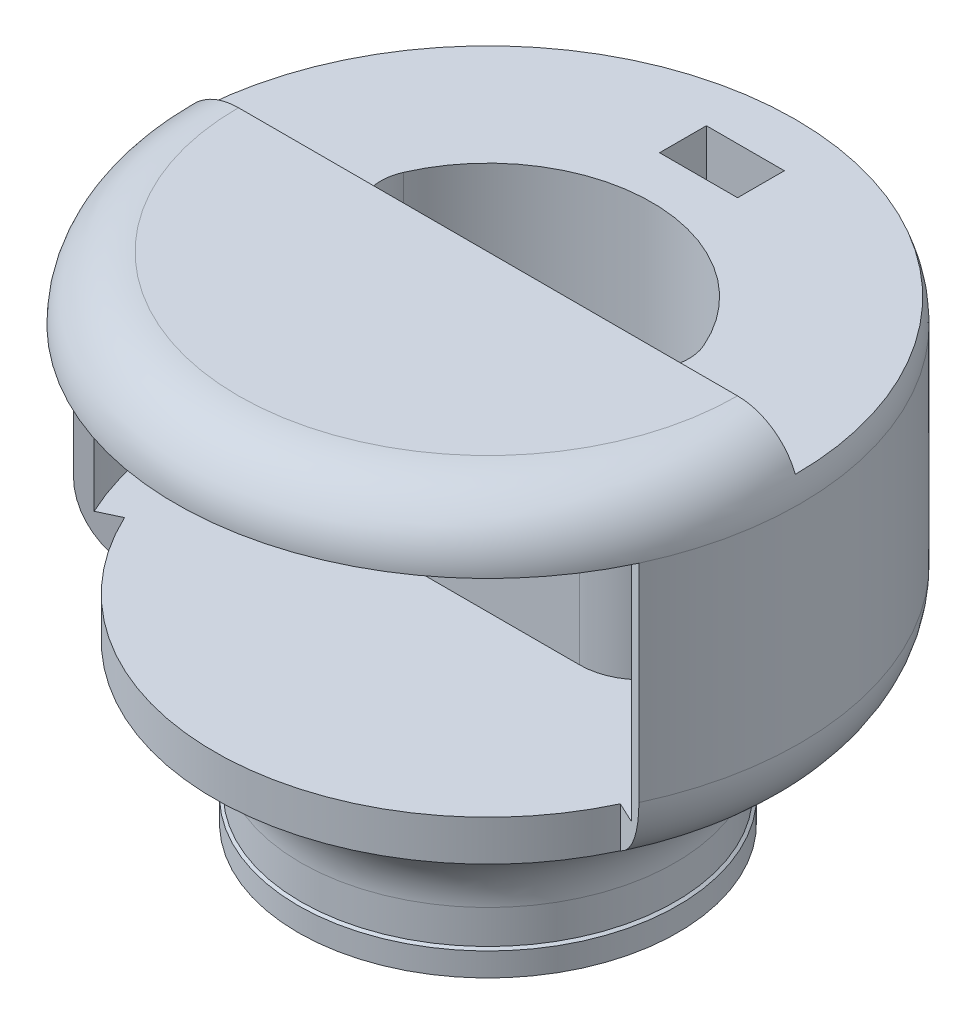
SolidWorks part; units mm, degrees
ref_plane "Front Plane" through (0, 0, 0) normal (0, 0, 1) x (1, 0, 0)
ref_plane "Top Plane" through (0, 0, 0) normal (0, 1, 0) x (1, 0, 0)
ref_plane "Right Plane" through (0, 0, 0) normal (1, 0, 0) x (0, 0, -1)
sketch "Sketch1" plane through (0, 0, 0) normal (0, 0, 1) x (1, 0, 0)
  line L0 (0, 0) -> (0, 90.2242) construction
  line L28 (0, 63.4279) -> (32, 63.4279)
  line L29 (40, 55.4279) -> (40, 28.8468)
  line L30 (22.5, 0) -> (24.35, 0)
  line L31 (24.35, 0) -> (24.35, 3)
  line L32 (24.35, 3) -> (24, 3.25)
  line L33 (24, 3.25) -> (24, 7.5811)
  line L34 (28.5399, 15.9588) -> (35.4601, 20.4691)
  line L35 (0, 13) -> (22, 13)
  line L36 (22.5, 12.5) -> (22.5, 0)
  line L37 (0, 13) -> (0, 63.4279)
  arc A0 (22, 13) -> (22.5, 12.5) centre (22, 12.5) cw
  arc A1 (24, 7.5811) -> (28.5399, 15.9588) centre (34, 7.5811) cw
  arc A2 (35.4601, 20.4691) -> (40, 28.8468) centre (30, 28.8468) ccw
  arc A3 (32, 63.4279) -> (40, 55.4279) centre (32, 55.4279) cw
  point P11 (22.9, 63.4279)
  point P18 (22.5, 13)
  point P21 (24, 13)
  point P24 (40, 23.4279)
  point P27 (40, 63.4279)
  point P28 (28.5604, 23.4279)
  point P31 (22.5, 17)
  dimension "D8" = 9.75
  dimension "D9" = 0.5
  dimension "D4" = 1.85
  dimension "D1" = 22.5
  dimension "D10" = 10
  dimension "D11" = 10
  dimension "D12" = 8
  dimension "D2" = 40
  dimension "D3" = 40
  dimension "D5" = 1.5
  dimension "D6" = 3
  dimension "D7" = 13
revolve "Revolve1" add sketch "Sketch1" angle 360 about L0
ref_plane "Plane1" through (0, 13, 0) normal (0, -1, 0) x (-1, 0, 0)
sketch "Sketch18" plane through (0, 0, 0) normal (0, 0, 1) x (1, 0, 0)
  line L0 (0, 0) -> (0, 101.5813) construction
  line L1 (-24.35, 0) -> (24.35, 0) construction
sketch "Sketch3" plane through (0, 0, 0) normal (0, 0, 1) x (1, 0, 0)
  point P0 (1.2404, 19.1989)
ref_point "Point1"
ref_plane "Plane2" through (0, 0, 22.9) normal (0, 0, 1) x (1, 0, 0)
ref_plane "Plane3" through (0, 0, 40) normal (0, 0, 1) x (1, 0, 0)
ref_plane "Plane4" through (0, 55.4279, 0) normal (0, 1, 0) x (1, 0, 0)
sketch "Sketch9" plane through (0, 55.4279, 0) normal (0, 1, 0) x (1, 0, 0)
  circle A7 centre (0, 0) radius 38
  circle A8 centre (0, 0) radius 40 construction
  circle A9 centre (0, 0) radius 23
  dimension "D1" = 2
  dimension "D2" = 46
ref_plane "Plane5" through (0, 13, 0) normal (0, -1, 0) x (-1, 0, 0)
sketch "Sketch11" plane through (0, 13, 0) normal (0, -1, 0) x (-1, 0, 0)
  line L0 (-21, 0) -> (21, 0)
  arc A1 (-21, 0) -> (21, 0) centre (0, 0) cw
  dimension "D1" = 42
extrude "Cut-Extrude3" cut sketch "Sketch11" against normal blind 60
ref_plane "Plane6" through (0, 0, -40) normal (0, 0, -1) x (-1, 0, 0)
extrude "Cut-Extrude5" cut sketch "Sketch9" against normal blind 30 and the other way blind 2
sketch "Sketch19" plane through (0, 0, 0) normal (1, 0, 0) x (0, 0, -1)
  line L0 (-47.0647, 55.4279) -> (-35.0647, 55.4279)
  line L1 (31.2976, 55.4279) -> (-31.2976, 55.4279) construction
  line L2 (-35.0647, 55.4279) -> (-35.0647, 18.9279)
  line L3 (-35.0647, 18.9279) -> (-47.0647, 18.9279)
  line L4 (-47.0647, 18.9279) -> (-47.0647, 55.4279)
  dimension "D1" = 12
  dimension "D2" = 36.5
revolve "Cut-Revolve2" cut sketch "Sketch19" angle 65 about L0 other way angle 65
ref_plane "Plane7" through (0, 0, 22.5) normal (0, 0, -1) x (-1, 0, 0)
sketch "Sketch21" plane through (0, 0, 22.5) normal (0, 0, -1) x (-1, 0, 0)
  line L0 (0, 0) -> (0, 101.5813) construction
  line L1 (-1.625, 4) -> (1.625, 4)
  line L2 (-1.625, 4) -> (-1.625, 0)
  line L3 (-1.625, 0) -> (1.625, 0)
  line L4 (1.625, 4) -> (1.625, 0)
  line L5 (-1.625, 4) -> (1.625, 0) construction
  line L6 (-1.625, 0) -> (1.625, 4) construction
  line L7 (-22.5, 0) -> (22.5, 0) construction
  point P0 (0, 2)
  dimension "D1" = 4
  dimension "D2" = 3.25
extrude "Boss-Extrude3" add sketch "Sketch21" along normal blind 1.35
pattern_circular "CirPattern1" count 5 over 360 about axis through (0, 0, 0) along (0, -1, 0) of "Boss-Extrude3"
ref_plane "Plane8" through (0, 20.4691, 0) normal (0, 1, 0) x (1, 0, 0)
sketch "Sketch22" plane through (0, 63.4279, 0) normal (0, 1, 0) x (1, 0, 0)
  line L0 (-40, 0) -> (40, 0)
  arc A0 (-40, 0) -> (40, 0) centre (0, 0) cw
  arc A1 (36.2523, -16.9047) -> (-36.2523, -16.9047) centre (0, 0) ccw construction
extrude "Cut-Extrude9" cut sketch "Sketch22" against normal blind 5
sketch "Sketch23" plane through (0, 0, -40) normal (0, 0, -1) x (-1, 0, 0)
  line L0 (0, 0) -> (0, 101.5813) construction
  line L1 (31.2976, 55.4279) -> (-31.2976, 55.4279) construction
  circle A0 centre (0, 42.1379) radius 10.5
  dimension "D1" = 21
  dimension "D2" = 13.29
extrude "Cut-Extrude10" cut sketch "Sketch23" against normal blind 10
sketch "Sketch24" plane through (0, 58.4279, 0) normal (0, 1, 0) x (1, 0, 0)
  line L1 (-7.5, 34) -> (7.5, 34)
  line L2 (-7.5, 34) -> (-7.5, 26)
  line L3 (-7.5, 26) -> (7.5, 26)
  line L4 (7.5, 34) -> (7.5, 26)
  line L5 (-7.5, 34) -> (7.5, 26) construction
  line L6 (-7.5, 26) -> (7.5, 34) construction
  arc A0 (39.4162, 0) -> (-39.4162, 0) centre (0, 0) ccw construction
  point P0 (0, 30)
  dimension "D1" = 30
  dimension "D2" = 8
  dimension "D3" = 15
extrude "Boss-Extrude4" add sketch "Sketch24" against normal blind 8
sketch "Sketch26" plane through (0, 58.4279, 0) normal (0, 1, 0) x (1, 0, 0)
  line L1 (-5, 33) -> (5, 33)
  line L2 (-5, 33) -> (-5, 27)
  line L3 (-5, 27) -> (5, 27)
  line L4 (5, 33) -> (5, 27)
  line L5 (-5, 33) -> (5, 27) construction
  line L6 (-5, 27) -> (5, 33) construction
  arc A0 (39.4162, 0) -> (-39.4162, 0) centre (0, 0) ccw construction
  point P0 (0, 30)
  dimension "D1" = 30
  dimension "D2" = 6
  dimension "D3" = 10
extrude "Cut-Extrude11" cut sketch "Sketch26" against normal blind 10
sketch "Sketch27" plane through (7.5, 0, 0) normal (1, 0, 0) x (0, 0, -1)
  line L0 (34, 50.4279) -> (34, 57.4279) construction
  line L1 (28, 56.4279) -> (32, 56.4279)
  line L2 (28, 56.4279) -> (28, 51.4279)
  line L3 (28, 51.4279) -> (32, 51.4279)
  line L4 (32, 56.4279) -> (32, 51.4279)
  line L5 (28, 56.4279) -> (32, 51.4279) construction
  line L6 (28, 51.4279) -> (32, 56.4279) construction
  line L7 (26, 50.4279) -> (26, 57.4279) construction
  line L8 (26, 50.4279) -> (34, 50.4279) construction
  point P0 (30, 53.9279)
  dimension "D1" = 8
  dimension "D2" = 3.5
  dimension "D3" = 5
  dimension "D4" = 4
extrude "Cut-Extrude12" cut sketch "Sketch27" against normal blind 5
ref_plane "Plane9" through (-39.4162, 58.4279, 0) normal (0.375, 0.927, 0) x (0.927, -0.375, 0)
ref_plane "Plane10" through (0, 58.4279, 0) normal (0, 1, 0) x (1, 0, 0)
sketch "Sketch28" plane through (0, 55.4279, 0) normal (0, 1, 0) x (1, 0, 0)
  line L0 (-22.9129, -2) -> (22.9129, -2)
  arc A0 (-22.9129, -2) -> (22.9129, -2) centre (0, 0) ccw
  dimension "D1" = 46
  dimension "D2" = 2
extrude "Cut-Extrude14" cut sketch "Sketch28" against normal blind 30 and the other way blind 2
sketch "Sketch29" plane through (0, 0, 0) normal (0, 0, -1) x (-1, 0, 0)
  line L0 (0, 0) -> (0, 101.5813) construction
  line L1 (32, 63.4279) -> (-32, 63.4279) construction
  circle A0 centre (-30.4162, 60.9279) radius 1
  circle A1 centre (30.4162, 60.9279) radius 1
  circle A2 centre (0, 60.9279) radius 1
  dimension "D1" = 2
  dimension "D2" = 2
  dimension "D3" = 2
  dimension "D4" = 2.5
  dimension "D5" = 2.5
  dimension "D6" = 2.5
  dimension "D7" = 9
  dimension "D8" = 9
extrude "Cut-Extrude15" cut sketch "Sketch29" against normal blind 15
fillet "Fillet1" radius 6 2 edges at (-21, 35.7139, 0) (21, 35.7139, 0)
fillet "Fillet2" radius 8 2 edges at (22.9129, 41.4279, 2) (-22.9129, 41.4279, 2)
